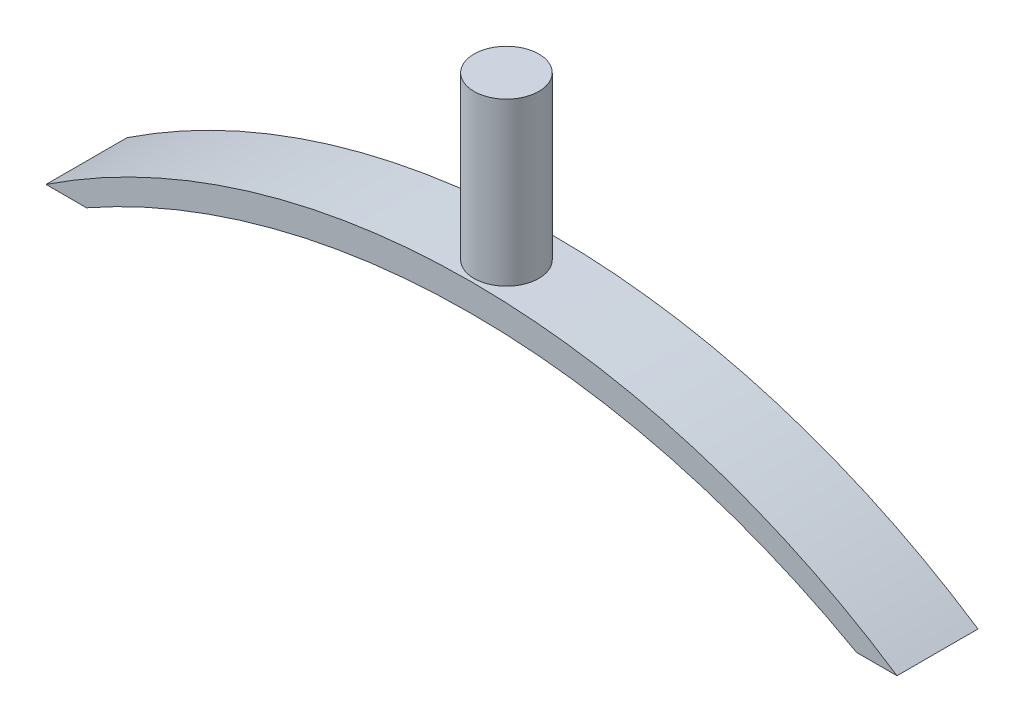
SolidWorks part; units mm, degrees
ref_plane "Front Plane" through (0, 0, 0) normal (0, 0, 1) x (1, 0, 0)
ref_plane "Top Plane" through (0, 0, 0) normal (0, 1, 0) x (1, 0, 0)
ref_plane "Right Plane" through (0, 0, 0) normal (1, 0, 0) x (0, 0, -1)
sketch "Sketch1" plane through (0, 0, 0) normal (0, 0, 1) x (1, 0, 0)
  line L0 (0, 0) -> (5, 0)
  line L1 (105.0571, 0) -> (100.0571, 0)
  arc A0 (0, 0) -> (105.0571, 0) centre (52.5286, -79.1312) cw
  arc A1 (5, 0) -> (100.0571, 0) centre (52.5286, -84.4689) cw
extrude "Boss-Extrude1" add sketch "Sketch1" along normal blind 10
scale "Scale1" scale about centroid uniform scaling yes scale factor 0.5
ref_plane "Plane5" through (0, 12.7861, 0) normal (0, 1, 0) x (1, 0, 0)
sketch "Sketch9" plane through (0, 12.7861, 0) normal (0, 1, 0) x (1, 0, 0)
  circle A0 centre (52.4255, -5.2401) radius 2
  dimension "D1" = 4
extrude "Boss-Extrude3" add sketch "Sketch9" along normal blind 10 separate body
